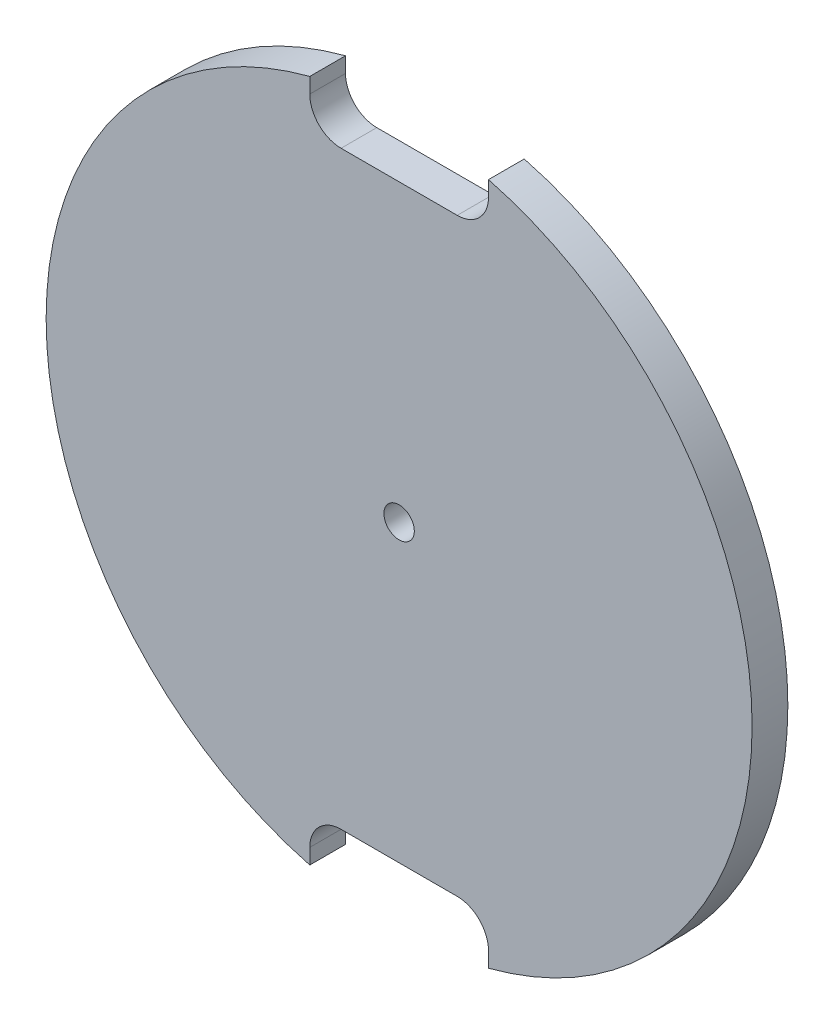
SolidWorks part; units mm, degrees
ref_plane "Płaszczyzna przednia" through (0, 0, 0) normal (0, 0, 1) x (1, 0, 0)
ref_plane "Płaszczyzna górna" through (0, 0, 0) normal (0, 1, 0) x (1, 0, 0)
ref_plane "Płaszczyzna prawa" through (0, 0, 0) normal (1, 0, 0) x (0, 0, -1)
sketch "Sketch1" plane through (0, 0, 0) normal (0, 0, 1) x (1, 0, 0)
  circle A0 centre (-12.8255, 19.2383) radius 39.5
extrude "Boss-Extrude1" add sketch "Sketch1" along normal blind 4
sketch "Sketch3" plane through (0, 0, 4) normal (0, 0, 1) x (1, 0, 0)
  circle A0 centre (-12.8255, 19.2383) radius 35
sketch "Sketch6" plane through (0, 0, 4) normal (0, 0, 1) x (1, 0, 0)
  line L0 (-12.8255, 54.2383) -> (-12.8255, -15.7617)
  line L1 (-47.8255, 19.2383) -> (22.1745, 19.2383)
  circle A0 centre (-12.8255, 19.2383) radius 35 construction
sketch "Sketch5" plane through (0, 0, 4) normal (0, 0, 1) x (1, 0, 0)
  line L0 (-19.3255, 59.2383) -> (-6.3255, 59.2383)
  line L1 (-19.3255, -13.7617) -> (-6.3255, -13.7617)
  line L2 (-19.3255, -13.7617) -> (-19.3255, -20.7617)
  line L3 (-19.3255, -20.7617) -> (-6.3255, -20.7617)
  line L4 (-6.3255, -13.7617) -> (-6.3255, -20.7617)
  line L5 (-19.3255, 59.2383) -> (-19.3255, 52.2383)
  line L6 (-19.3255, 52.2383) -> (-6.3255, 52.2383)
  line L7 (-6.3255, 59.2383) -> (-6.3255, 52.2383)
  line L17 (-12.8255, 54.2383) -> (-12.8255, -15.7617) construction
  line L22 (-22.8255, -17.2617) -> (-22.8255, -22.0586)
  line L23 (-22.8255, -22.0586) -> (-2.8255, -22.0586)
  line L24 (-2.8255, -22.0586) -> (-2.8255, -17.2617)
  line L25 (-2.8255, -17.2617) -> (-22.8255, -17.2617)
  line L30 (-22.8255, 55.7383) -> (-22.8255, 60.1835)
  line L31 (-22.8255, 60.1835) -> (-2.8255, 60.1835)
  line L32 (-2.8255, 60.1835) -> (-2.8255, 55.7383)
  line L33 (-2.8255, 55.7383) -> (-22.8255, 55.7383)
  arc A0 (-6.3255, -13.7617) -> (-6.3255, -20.7617) centre (-6.3255, -17.2617) cw
  arc A1 (-19.3255, -13.7617) -> (-19.3255, -20.7617) centre (-19.3255, -17.2617) ccw
  arc A2 (-6.3255, 59.2383) -> (-6.3255, 52.2383) centre (-6.3255, 55.7383) cw
  arc A3 (-19.3255, 59.2383) -> (-19.3255, 52.2383) centre (-19.3255, 55.7383) ccw
  circle A8 centre (-12.8255, 19.2383) radius 39.5 construction
  dimension "D1" = 13
  dimension "D2" = 7
  dimension "D3" = 13
  dimension "D4" = 7
  dimension "D10" = 40
  dimension "D12" = 40
  dimension "D13" = 6.5
  dimension "D15" = 6.5
extrude "Cut-Extrude2" cut sketch "Sketch5" against normal blind 10 contours A2 L7 | L5 A3 | L2 A1 | L4 L1 L2 L3 | A0 L4 | L7 L33 L5 L6 | L33 L30 L31 L32 | L25 L22 L23 L24 region at (-12.8255, 53.9883, 4) region at (-20.811, 54.2529, 4) region at (-4.8401, 54.2529, 4) region at (-12.8255, -15.5117, 4) region at (-20.811, -15.7762, 4) region at (-4.8401, -15.7762, 4)
sketch "Sketch7" plane through (0, 0, 0) normal (0, 0, -1) x (-1, 0, 0)
  circle A0 centre (12.8255, 19.2383) radius 26
extrude "Boss-Extrude2" add sketch "Sketch7" along normal blind 7
sketch "Sketch8" plane through (0, 0, 4) normal (0, 0, 1) x (1, 0, 0)
  circle A0 centre (-12.8255, 19.2383) radius 1.7
extrude "Cut-Extrude3" cut sketch "Sketch8" against normal blind 20
sketch "Sketch9" plane through (0, 0, 4) normal (0, 0, 1) x (1, 0, 0)
  circle A0 centre (-12.8255, 19.2383) radius 5
extrude "Cut-Extrude4" cut sketch "Sketch9" against normal blind 20 from offset 7 offset against normal yes
